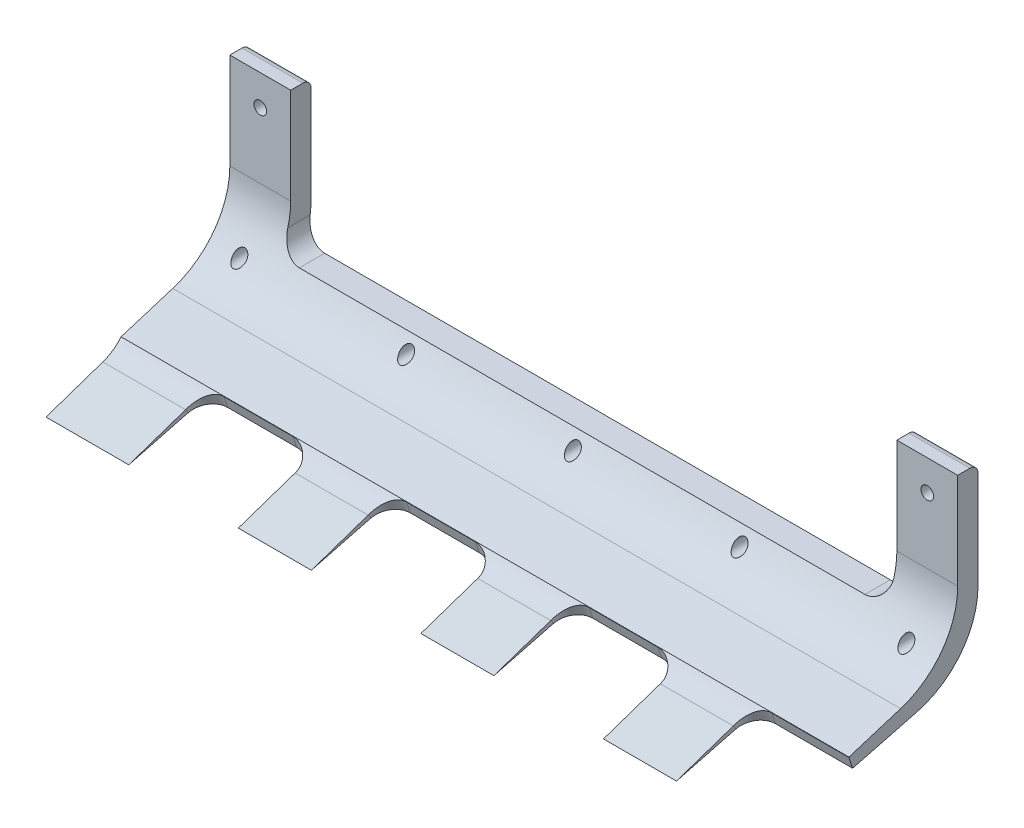
SolidWorks part; units mm, degrees
material "POLYURETHANE (11671)"
ref_plane "Front Plane" through (0, 0, 0) normal (0, 0, 1) x (1, 0, 0)
ref_plane "Top Plane" through (0, 0, 0) normal (0, 1, 0) x (1, 0, 0)
ref_plane "Right Plane" through (0, 0, 0) normal (1, 0, 0) x (0, 0, -1)
sketch "Sketch1" plane through (0, 0, 0) normal (1, 0, 0) x (0, 0, -1)
  line L0 (0, 51.1389) -> (0, 11.1389) construction
  line L1 (0, 11.1389) -> (-47.8152, -3.4796) construction
  line L2 (-2.5, 51.1389) -> (-2.5, 12.7316)
  line L3 (2.5, 51.1389) -> (2.5, 9.5463)
  line L6 (-2.5, 51.1389) -> (2.5, 51.1389)
  line L7 (2.5, 51.1389) -> (2.5, 11.1389) construction
  line L9 (-2.5, 51.1389) -> (-2.5, 11.1389) construction
  line L11 (-47.8152, -3.4796) -> (2.5, 9.5463)
  line L12 (-29.3124, 4.4065) -> (-28.4353, 1.5375) construction
  line L13 (-29.3124, 4.4065) -> (-2.5, 12.7316)
  line L14 (-47.8152, -3.4796) -> (-28.8739, 2.972)
  line L15 (-29.3124, 4.4065) -> (-28.8739, 2.972)
  point P11 (0, 0)
  point P12 (0, 0)
  point P18 (0, 0)
  dimension "D1" = 40
  dimension "D2" = 50
  dimension "D3" = 107
  dimension "D6" = 3
  dimension "D7" = 20
  dimension "D8" = 1.5
  dimension "D4" = 2.5
  dimension "D5" = 2.5
extrude "Boss-Extrude1" add sketch "Sketch1" along normal blind 179.4 contours L6 L2 L3 region at (0, 50.3963, 0)
fillet "Fillet1" radius 20 2 edges at (89.7, 9.5463, -2.5) (89.7, 12.7316, 2.5)
sketch "Sketch2" plane through (0, 0, 2.5) normal (0, 0, 1) x (1, 0, 0)
  line L0 (179.4, 51.1389) -> (0, 51.1389) construction
  line L1 (15, 51.1389) -> (164.4, 51.1389)
  line L2 (15, 51.1389) -> (15, 17.1389)
  line L3 (15, 17.1389) -> (164.4, 17.1389)
  line L4 (164.4, 51.1389) -> (164.4, 17.1389)
  line L5 (0, 51.1389) -> (0, 27.4636) construction
  line L6 (179.4, 51.1389) -> (179.4, 27.4636) construction
  dimension "D1" = 34
  dimension "D2" = 15
  dimension "D3" = 15
extrude "Cut-Extrude1" cut sketch "Sketch2" against normal mid plane 179.4
fillet "Fillet2" radius 5 2 edges at (164.4, 17.1389, 2.2463) (15, 17.1389, 2.2463)
fillet "Fillet3" radius 2 2 edges at (171.9, 51.1389, -2.5) (7.5, 51.1389, -2.5)
sketch "Sketch3" plane through (0, 0, 2.5) normal (0, 0, 1) x (1, 0, 0)
  line L0 (89.7, 61.7824) -> (89.7, 40.4955) construction
  line L2 (15, 51.1389) -> (0, 51.1389) construction
  line L3 (0, 51.1389) -> (0, 27.4636) construction
  line L5 (0, 51.1389) -> (179.4, 51.1389) construction
  circle A0 centre (7.5, 43.6389) radius 1.55
  circle A3 centre (171.9, 43.6389) radius 1.55
  point P4 (89.7, 51.1389)
  dimension "D1" = 3.1
  dimension "D2" = 7.5
  dimension "D3" = 7.5
extrude "Cut-Extrude2" cut sketch "Sketch3" against normal up to next
sketch "Sketch4" plane through (0, 0, 2.5) normal (0, 0, 1) x (1, 0, 0)
  line L0 (7.5, 43.6389) -> (7.5, -15.351) construction
  line L2 (7.5, 14.1389) -> (185.9379, 14.1389) construction
  line L3 (179.4, 51.1389) -> (179.4, 27.4636) construction
  line L4 (15, 51.1389) -> (0, 51.1389) construction
  circle A0 centre (7.5, 14.1389) radius 1.55
  circle A1 centre (48.6, 14.1389) radius 1.55
  circle A2 centre (89.7, 14.1389) radius 1.55
  circle A3 centre (130.8, 14.1389) radius 1.55
  circle A4 centre (171.9, 14.1389) radius 1.55
  dimension "D1" = 3.1
  dimension "D4" = 7.5
  dimension "D2" = 37
  dimension "D3" = 5
extrude "Cut-Extrude3" cut sketch "Sketch4" against normal mid plane 179.4
sketch "Sketch6" plane through (0, 11.4754, 3.9087) normal (0, 0.9466, 0.3224) x (1, 0, 0)
  line L0 (179.4, -46.3836) -> (179.4, -26.3737) construction
  line L1 (155.4, -26.3836) -> (182.4, -26.3836)
  line L2 (155.4, -26.3836) -> (155.4, -46.3836)
  line L3 (155.4, -46.3836) -> (182.4, -46.3836)
  line L4 (182.4, -26.3836) -> (182.4, -46.3836)
  line L5 (179.4, -46.3836) -> (0, -46.3836) construction
  line L6 (181.8363, -23.2066) -> (-12.22, -23.2066) construction
  line L7 (110.4, -26.3836) -> (110.4, -46.3836)
  line L8 (110.4, -26.3836) -> (137.4, -26.3836)
  line L9 (137.4, -26.3836) -> (137.4, -46.3836)
  line L10 (110.4, -46.3836) -> (137.4, -46.3836)
  line L11 (65.4, -26.3836) -> (65.4, -46.3836)
  line L12 (65.4, -26.3836) -> (92.4, -26.3836)
  line L13 (92.4, -26.3836) -> (92.4, -46.3836)
  line L14 (65.4, -46.3836) -> (92.4, -46.3836)
  line L15 (20.4, -26.3836) -> (20.4, -46.3836)
  line L16 (20.4, -26.3836) -> (47.4, -26.3836)
  line L17 (47.4, -26.3836) -> (47.4, -46.3836)
  line L18 (20.4, -46.3836) -> (47.4, -46.3836)
  dimension "D1" = 20
  dimension "D2" = 27
  dimension "D3" = 24
  dimension "D4" = 4
extrude "Cut-Extrude4" cut sketch "Sketch6" against normal up to next
fillet "Fillet4" radius 10 1 edges at (89.7, 2.972, 28.8739)
fillet "Fillet5" radius 5 7 edges at (47.4, 2.9508, 28.8772) (92.4, 2.9508, 28.8772) (137.4, 2.9508, 28.8772) (155.4, 2.9508, 28.8772) (110.4, 2.9508, 28.8772) (65.4, 2.9508, 28.8772) (20.4, 2.9508, 28.8772)
